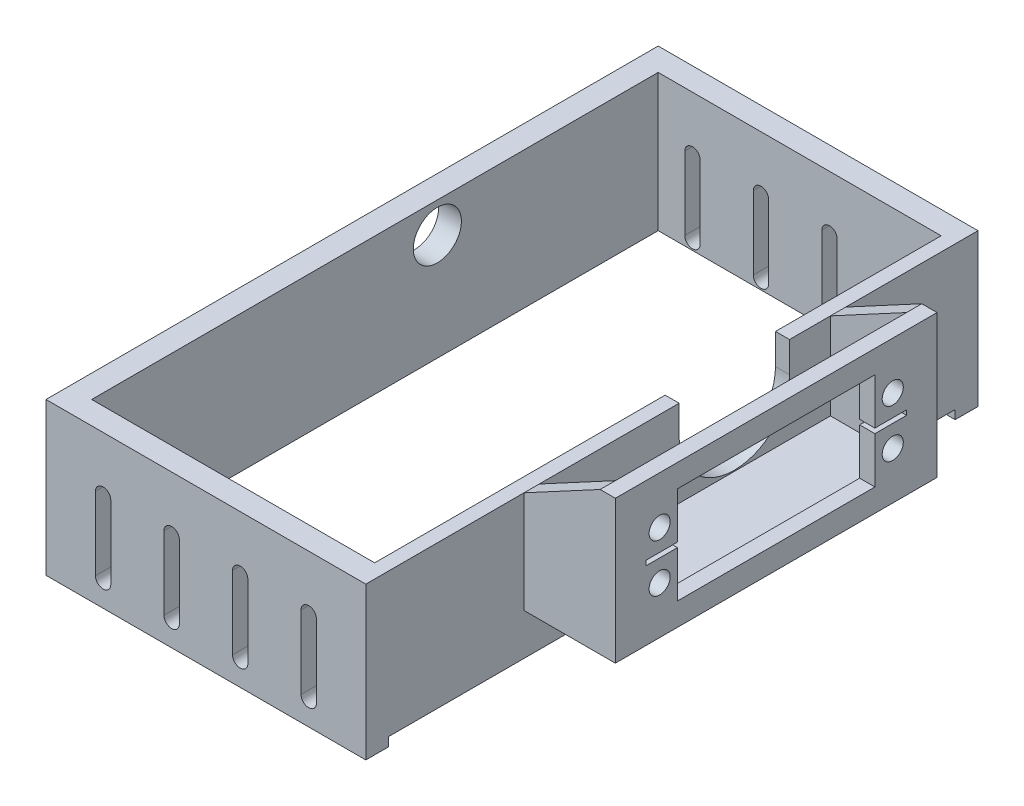
SolidWorks part; units mm, degrees
ref_plane "Front Plane" through (0, 0, 0) normal (0, 0, 1) x (1, 0, 0)
ref_plane "Top Plane" through (0, 0, 0) normal (0, 1, 0) x (1, 0, 0)
ref_plane "Right Plane" through (0, 0, 0) normal (1, 0, 0) x (0, 0, -1)
sketch "Sketch2" plane through (0, 0, 0) normal (0, 1, 0) x (1, 0, 0)
  line L0 (-33.3375, -63.8125) -> (-33.3375, 63.8125)
  line L1 (-28.575, -59.05) -> (28.575, -59.05)
  line L2 (-28.575, -59.05) -> (-28.575, 59.05)
  line L3 (-28.575, 59.05) -> (28.575, 59.05)
  line L4 (28.575, -59.05) -> (28.575, 59.05)
  line L5 (-28.575, -59.05) -> (28.575, 59.05) construction
  line L6 (-28.575, 59.05) -> (28.575, -59.05) construction
  line L7 (-33.3375, 63.8125) -> (33.3375, 63.8125)
  line L8 (33.3375, -63.8125) -> (33.3375, 63.8125)
  line L9 (-33.3375, -63.8125) -> (33.3375, -63.8125)
  line L10 (0, 59.05) -> (0, -59.05)
  line L11 (-14.2875, 59.05) -> (-14.2875, -59.05)
  line L12 (14.2875, 59.05) -> (14.2875, -59.05)
  line L13 (-28.575, 0) -> (-14.2875, 0) construction
  line L14 (-14.2875, 0) -> (0, 0) construction
  line L15 (0, 0) -> (14.2875, 0) construction
  line L16 (14.2875, 0) -> (28.575, 0) construction
  point P0 (0, 0)
  dimension "D1" = 118.1
  dimension "D2" = 57.15
  dimension "D3" = 4.7625
sketch "Sketch3" plane through (0, 0, 0) normal (0, 0, 1) x (1, 0, 0)
  line L0 (0, 0) -> (0, 12.7) construction
  line L1 (-28.575, 0) -> (28.575, 0) construction
  line L2 (0, 12.7) -> (0, 19.05) construction
  dimension "D1" = 12.7
  dimension "D2" = 6.35
sketch "Sketch4" plane through (0, 0, 0) normal (0, 1, 0) x (1, 0, 0)
  line L4 (-28.575, -59.05) -> (28.575, -59.05)
  line L5 (28.575, -59.05) -> (28.575, 59.05)
  line L6 (28.575, 59.05) -> (-28.575, 59.05)
  line L7 (-28.575, 59.05) -> (-28.575, -59.05)
  line L8 (-28.575, -59.05) -> (28.575, -59.05)
  line L9 (28.575, -59.05) -> (28.575, 59.05)
  line L10 (28.575, 59.05) -> (-28.575, 59.05)
  line L11 (-28.575, 59.05) -> (-28.575, -59.05)
  line L12 (-33.3375, 63.8125) -> (-33.3375, -63.8125)
  line L13 (33.3375, 63.8125) -> (-33.3375, 63.8125)
  line L14 (33.3375, -63.8125) -> (33.3375, 63.8125)
  line L15 (-33.3375, -63.8125) -> (33.3375, -63.8125)
  line L16 (-33.3375, 63.8125) -> (-33.3375, -63.8125)
  line L17 (33.3375, 63.8125) -> (-33.3375, 63.8125)
  line L18 (33.3375, -63.8125) -> (33.3375, 63.8125)
  line L19 (-33.3375, -63.8125) -> (33.3375, -63.8125)
  dimension "D1" = 0
  dimension "D2" = 0
extrude "Boss-Extrude1" add sketch "Sketch4" along normal up to vertex (19.05 mm away) up to point (0, 19.05, 0)
sketch "Sketch5" plane through (0, 0, 0) normal (0, 1, 0) x (1, 0, 0)
  line L0 (-33.3375, -63.8125) -> (33.3375, -63.8125) construction
  line L1 (33.3375, -63.8125) -> (33.3375, 63.8125) construction
  line L2 (-33.3375, 63.8125) -> (33.3375, 63.8125) construction
  line L3 (-33.3375, -63.8125) -> (-33.3375, 63.8125) construction
  line L4 (-33.3375, -63.8125) -> (33.3375, -63.8125)
  line L5 (33.3375, -63.8125) -> (33.3375, 63.8125)
  line L6 (-33.3375, 63.8125) -> (33.3375, 63.8125)
  line L7 (-33.3375, -63.8125) -> (-33.3375, 63.8125)
extrude "Boss-Extrude2" add sketch "Sketch5" along normal blind 12.7 from surface contours L4 L5 L6 L7 starting at face at (0, 19.05, 0)
fillet "Fillet1" radius 3.175 4 edges at (0, 0, -59.05) (0, 0, 59.05) (28.575, 0, 0) (-28.575, 0, 0) profile chamfer
sketch "Sketch14" plane through (0, 19.05, 0) normal (0, -1, 0) x (1, 0, 0)
  line L1 (-28.575, 59.05) -> (28.575, 59.05)
  line L2 (-28.575, 59.05) -> (-28.575, -59.05)
  line L3 (-28.575, -59.05) -> (28.575, -59.05)
  line L4 (28.575, 59.05) -> (28.575, -59.05)
extrude "Cut-Extrude8" cut sketch "Sketch14" against normal up to surface (12.7 mm away) up to face at (0, 31.75, 0)
sketch "Sketch26" plane through (0, 31.75, 0) normal (0, 1, 0) x (1, 0, 0)
  line L0 (-28.575, -59.05) -> (28.575, -59.05) construction
  line L1 (28.575, 59.05) -> (30.4165, 59.05)
  line L2 (28.575, 59.05) -> (28.575, -59.05)
  line L3 (28.575, -59.05) -> (30.4165, -59.05)
  line L4 (30.4165, 59.05) -> (30.4165, -59.05)
  dimension "D1" = 1.8415
extrude "Cut-Extrude11" cut sketch "Sketch26" against normal through all
sketch "Sketch27" plane through (33.3375, 0, 0) normal (1, 0, 0) x (0, 0, -1)
  line L0 (-63.8125, 0) -> (63.8125, 0) construction
  line L1 (-59.05, 0) -> (59.05, 0)
  line L2 (-59.05, 0) -> (-59.05, 1.8415)
  line L3 (-59.05, 1.8415) -> (59.05, 1.8415)
  line L4 (59.05, 0) -> (59.05, 1.8415)
  dimension "D1" = 1.8415
extrude "Cut-Extrude12" cut sketch "Sketch27" against normal up to next
sketch "Sketch30" plane through (-33.3375, 0, 0) normal (-1, 0, 0) x (0, 0, 1)
  line L0 (-59.05, 0) -> (59.05, 0) construction
  line L1 (-63.8125, 31.75) -> (-63.8125, 0) construction
  circle A0 centre (-13.0125, 25.4) radius 5.0165
  dimension "D1" = 10.033
  dimension "D2" = 25.4
  dimension "D3" = 50.8
extrude "Cut-Extrude13" cut sketch "Sketch30" against normal through all
sketch "Sketch31" plane through (33.3375, 0, 0) normal (1, 0, 0) x (0, 0, -1)
  line L5 (1.5125, 25.4) -> (1.5125, 31.75)
  line L7 (1.5125, 31.75) -> (24.5125, 31.75)
  line L8 (63.8125, 31.75) -> (-63.8125, 31.75) construction
  line L9 (24.5125, 31.75) -> (24.5125, 25.4)
  arc A0 (1.5125, 25.4) -> (24.5125, 25.4) centre (13.0125, 25.4) ccw
  point P2 (36.2125, 25.4)
  point P4 (1.5125, 31.75)
  point P5 (1.5125, 31.75)
  point P6 (1.5125, 25.4)
  dimension "D1" = 23
extrude "Cut-Extrude16" cut sketch "Sketch31" against normal up to surface (2.921 mm away) up to face at (30.4165, 25.4, -18.029)
sketch "Sketch32" plane through (33.3375, 0, 0) normal (1, 0, 0) x (0, 0, -1)
  line L12 (23.2665, 15.273) -> (23.2665, 24.9)
  line L13 (-17.8875, 15.273) -> (23.2665, 15.273)
  line L14 (-17.8875, 24.9) -> (-17.8875, 15.273)
  line L15 (-24.4915, 24.9) -> (-17.8875, 24.9)
  line L16 (-24.4915, 25.9) -> (-24.4915, 24.9)
  line L17 (-17.8875, 25.9) -> (-24.4915, 25.9)
  line L18 (-17.8875, 35.527) -> (-17.8875, 25.9)
  line L19 (23.2665, 35.527) -> (-17.8875, 35.527)
  line L20 (23.2665, 25.9) -> (23.2665, 35.527)
  line L21 (29.8705, 25.9) -> (23.2665, 25.9)
  line L22 (29.8705, 24.9) -> (29.8705, 25.9)
  line L23 (23.2665, 24.9) -> (29.8705, 24.9)
  line L24 (23.2665, 15.273) -> (23.2665, 24.9)
  line L25 (-17.8875, 15.273) -> (23.2665, 15.273)
  line L26 (-17.8875, 24.9) -> (-17.8875, 15.273)
  line L27 (-24.4915, 24.9) -> (-17.8875, 24.9)
  line L28 (-24.4915, 25.9) -> (-24.4915, 24.9)
  line L29 (-17.8875, 25.9) -> (-24.4915, 25.9)
  line L30 (-17.8875, 35.527) -> (-17.8875, 25.9)
  line L31 (23.2665, 35.527) -> (-17.8875, 35.527)
  line L32 (23.2665, 25.9) -> (23.2665, 35.527)
  line L33 (29.8705, 25.9) -> (23.2665, 25.9)
  line L34 (29.8705, 24.9) -> (29.8705, 25.9)
  line L35 (23.2665, 24.9) -> (29.8705, 24.9)
  circle A1 centre (26.9895, 30.4) radius 2.2
  circle A2 centre (26.9895, 30.4) radius 2.2
  circle A3 centre (26.9895, 20.4) radius 2.2
  circle A4 centre (26.9895, 20.4) radius 2.2
  circle A5 centre (-21.6105, 30.4) radius 2.2
  circle A6 centre (-21.6105, 30.4) radius 2.2
  circle A7 centre (-21.6105, 20.4) radius 2.2
  circle A8 centre (-21.6105, 20.4) radius 2.2
  point P14 (13.0125, 25.4)
  point P16 (-7.6335, 25.4)
  dimension "D1" = 0
  dimension "D2" = 0
  dimension "D3" = 0
  dimension "D4" = 0
  dimension "D5" = 0
sketch "Sketch33" plane through (33.3375, 0, 0) normal (1, 0, 0) x (0, 0, -1)
  line L0 (1.5125, 31.75) -> (-63.8125, 31.75) construction
  line L2 (-27.6665, 31.75) -> (-27.6665, 13.6855)
  line L3 (-27.6665, 13.6855) -> (33.0455, 13.6855)
  line L4 (33.0455, 31.75) -> (33.0455, 13.6855)
  line L5 (-17.8875, 15.273) -> (23.2665, 15.273) construction
  line L6 (-24.4915, 25.9) -> (-24.4915, 24.9) construction
  line L7 (29.8705, 24.9) -> (29.8705, 25.9) construction
  line L8 (-30.8415, 31.75) -> (-30.8415, 10.5105)
  line L9 (-30.8415, 10.5105) -> (36.2205, 10.5105)
  line L10 (36.2205, 31.75) -> (36.2205, 10.5105)
  line L12 (-30.8415, 31.75) -> (-27.6665, 31.75)
  line L13 (63.8125, 31.75) -> (24.5125, 31.75) construction
  line L14 (-30.8415, 34.925) -> (-30.8415, 10.5105) construction
  line L15 (-30.8415, 34.925) -> (36.2205, 34.925) construction
  line L16 (36.2205, 34.925) -> (36.2205, 10.5105) construction
  line L17 (-27.6665, 31.75) -> (33.0455, 31.75) construction
  line L18 (33.0455, 31.75) -> (36.2205, 31.75)
  dimension "D1" = 1.5875
  dimension "D2" = 3.175
  dimension "D3" = 3.175
  dimension "D4" = 3.175
extrude "Boss-Extrude4" add sketch "Sketch33" along normal blind 19.05
sketch "Sketch34" plane through (52.3875, 0, 0) normal (1, 0, 0) x (0, 0, -1)
  line L0 (23.2665, 35.527) -> (-17.8875, 35.527) construction
  line L1 (36.2205, 10.5105) -> (-30.8415, 10.5105)
  line L2 (36.2205, 10.5105) -> (36.2205, 40.2895)
  line L3 (36.2205, 40.2895) -> (-30.8415, 40.2895)
  line L4 (-30.8415, 10.5105) -> (-30.8415, 40.2895)
  dimension "D1" = 4.7625
extrude "Boss-Extrude5" add sketch "Sketch34" against normal blind 3.175
extrude "Cut-Extrude17" cut sketch "Sketch32" against normal up to surface (-15.875 mm away) from surface up to face at (49.2125, 29.3687, -2.6895) starting at face at (52.3875, 25.4, -2.6895)
sketch "Sketch35" plane through (0, 0, -36.2205) normal (0, 0, -1) x (-1, 0, 0)
  line L0 (-49.2125, 40.2895) -> (-33.3375, 31.75)
  line L1 (-33.3375, 31.75) -> (-49.2125, 31.75)
  line L2 (-49.2125, 31.75) -> (-49.2125, 40.2895)
extrude "Boss-Extrude6" add sketch "Sketch35" against normal blind 3.175
extrude "Boss-Extrude8" add sketch "Sketch35<2>" against normal blind 3.175 from surface starting at face at (41.275, 22.7178, 27.6665)
sketch "Sketch35<2>" plane through (0, 0, -36.2205) normal (0, 0, -1) x (-1, 0, 0) same geometry as "Sketch35"
sketch "Sketch40" plane through (0, 0, -63.8125) normal (0, 0, -1) x (-1, 0, 0)
  line L0 (-7.1438, 20.32) -> (-7.1438, 5.08) construction
  line L1 (-5.5437, 20.32) -> (-5.5437, 5.08)
  line L2 (-8.7438, 20.32) -> (-8.7438, 5.08)
  line L3 (-33.3375, 0) -> (33.3375, 0) construction
  line L4 (7.1437, 20.32) -> (7.1437, 5.08) construction
  line L5 (8.7438, 20.32) -> (8.7438, 5.08)
  line L6 (5.5437, 20.32) -> (5.5437, 5.08)
  line L7 (21.4312, 20.32) -> (21.4312, 5.08) construction
  line L8 (23.0313, 20.32) -> (23.0313, 5.08)
  line L9 (19.8312, 20.32) -> (19.8312, 5.08)
  line L11 (-21.4313, 20.32) -> (-21.4313, 5.08) construction
  line L12 (-19.8312, 20.32) -> (-19.8312, 5.08)
  line L13 (-23.0313, 20.32) -> (-23.0313, 5.08)
  arc A0 (-5.5437, 20.32) -> (-8.7438, 20.32) centre (-7.1438, 20.32) ccw
  arc A1 (-8.7438, 5.08) -> (-5.5437, 5.08) centre (-7.1438, 5.08) ccw
  arc A2 (8.7438, 20.32) -> (5.5437, 20.32) centre (7.1437, 20.32) ccw
  arc A3 (5.5437, 5.08) -> (8.7438, 5.08) centre (7.1437, 5.08) ccw
  arc A4 (23.0313, 20.32) -> (19.8312, 20.32) centre (21.4312, 20.32) ccw
  arc A5 (19.8312, 5.08) -> (23.0313, 5.08) centre (21.4312, 5.08) ccw
  arc A6 (-19.8312, 20.32) -> (-23.0313, 20.32) centre (-21.4313, 20.32) ccw
  arc A7 (-23.0313, 5.08) -> (-19.8312, 5.08) centre (-21.4313, 5.08) ccw
  point P2 (-7.1438, 12.7)
  point P14 (7.1437, 12.7)
  point P21 (21.4312, 12.7)
  point P31 (-21.4313, 12.7)
  dimension "D3" = 1.6
  dimension "D1" = 7.1437
  dimension "D2" = 5.08
  dimension "D4" = 1.27
  dimension "D6" = 14.2875
  dimension "D8" = 14.2875
  dimension "D5" = 3
  dimension "D7" = 2
extrude "Cut-Extrude18" cut sketch "Sketch40" against normal through all both and the other way through all
equation "\"tighttol\" = 0.005in"
equation "\"normtol\" = 0.01in"
equation "\"loosetol\" = 0.02in"
equation "\"Fry height\"= 0.5in"
equation "\"Fry spacing\"= 0.5625in"
equation "\"Potato width\"= \"Fry spacing\" * 4"
equation "\"Potato length\"= 80mm"
equation "\"D2@Sketch2\"=\"Potato width\""
equation "\"D1@Sketch3\"=\"Fry height\""
equation "\"D1@Sketch2\"=\"Potato length\"+1.5"
equation "\"D1@Sketch27\"=0.062500in+\"normtol\""
equation "\"D1@Sketch26\"=0.0625+\"normtol\""
equation "\"D1@Sketch31\"=23mm"
equation "\"D1@Sketch40\"=\"Fry spacing\"/2"
equation "\"D3@Sketch40\"=1.6mm"
equation "\"D6@Sketch40\"=\"Fry spacing\""
equation "\"D8@Sketch40\"=\"Fry spacing\""
